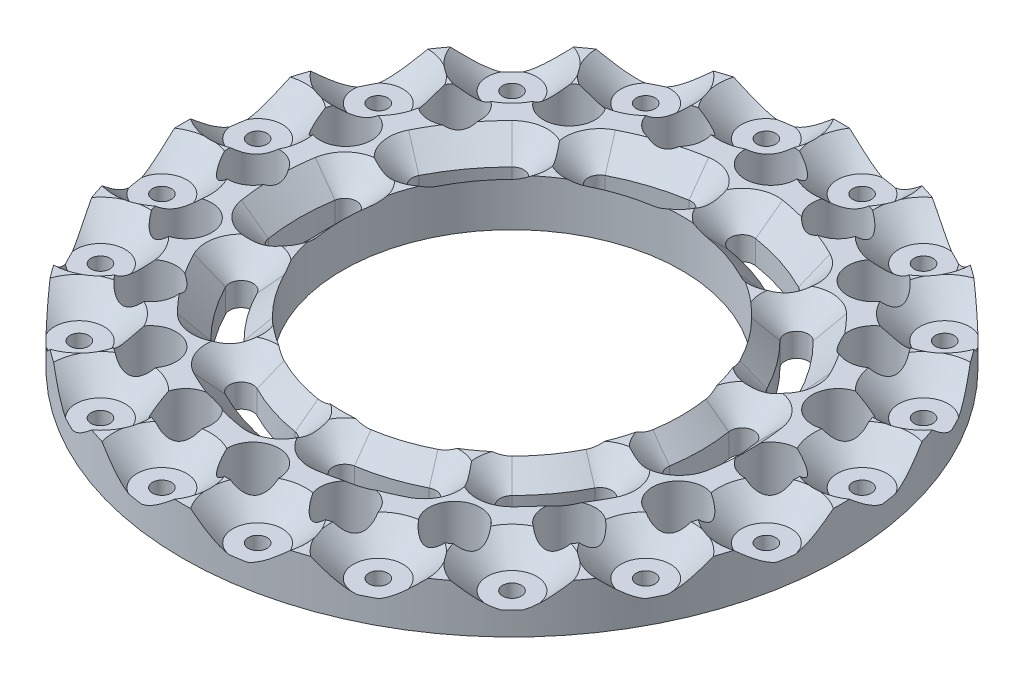
SolidWorks part; units mm, degrees
ref_plane "Front Plane" through (0, 0, 0) normal (0, 0, 1) x (1, 0, 0)
ref_plane "Top Plane" through (0, 0, 0) normal (0, 1, 0) x (1, 0, 0)
ref_plane "Right Plane" through (0, 0, 0) normal (1, 0, 0) x (0, 0, -1)
sketch "Sketch1" plane through (0, 0, 0) normal (0, 1, 0) x (1, 0, 0)
  circle A1 centre (55, 0) radius 5.5
  circle A2 centre (52.3081, -16.9959) radius 5.5
  circle A3 centre (44.4959, -32.3282) radius 5.5
  circle A4 centre (32.3282, -44.4959) radius 5.5
  circle A5 centre (16.9959, -52.3081) radius 5.5
  circle A6 centre (0, -55) radius 5.5
  circle A7 centre (-16.9959, -52.3081) radius 5.5
  circle A8 centre (-32.3282, -44.4959) radius 5.5
  circle A9 centre (-44.4959, -32.3282) radius 5.5
  circle A10 centre (-52.3081, -16.9959) radius 5.5
  circle A11 centre (-55, 0) radius 5.5
  circle A12 centre (-52.3081, 16.9959) radius 5.5
  circle A13 centre (-44.4959, 32.3282) radius 5.5
  circle A14 centre (-32.3282, 44.4959) radius 5.5
  circle A15 centre (-16.9959, 52.3081) radius 5.5
  circle A16 centre (0, 55) radius 5.5
  circle A17 centre (16.9959, 52.3081) radius 5.5
  circle A18 centre (32.3282, 44.4959) radius 5.5
  circle A19 centre (44.4959, 32.3282) radius 5.5
  circle A20 centre (52.3081, 16.9959) radius 5.5
  circle A21 centre (0, 0) radius 36
  circle A22 centre (0, 0) radius 70
  circle A24 centre (64.1997, 10.1682) radius 2
  circle A25 centre (64.1997, -10.1682) radius 2
  circle A26 centre (57.9154, -29.5094) radius 2
  circle A27 centre (45.9619, -45.9619) radius 2
  circle A28 centre (29.5094, -57.9154) radius 2
  circle A29 centre (10.1682, -64.1997) radius 2
  circle A30 centre (-10.1682, -64.1997) radius 2
  circle A31 centre (-29.5094, -57.9154) radius 2
  circle A32 centre (-45.9619, -45.9619) radius 2
  circle A33 centre (-57.9154, -29.5094) radius 2
  circle A34 centre (-64.1997, -10.1682) radius 2
  circle A35 centre (-64.1997, 10.1682) radius 2
  circle A36 centre (-57.9154, 29.5094) radius 2
  circle A37 centre (-45.9619, 45.9619) radius 2
  circle A38 centre (-29.5094, 57.9154) radius 2
  circle A39 centre (-10.1682, 64.1997) radius 2
  circle A40 centre (10.1682, 64.1997) radius 2
  circle A41 centre (29.5094, 57.9154) radius 2
  circle A42 centre (45.9619, 45.9619) radius 2
  circle A43 centre (57.9154, 29.5094) radius 2
  point P46 (0, 0)
  point P92 (0, 0)
  dimension "D1" = 20
  dimension "D3" = 20
extrude "Boss-Extrude1" add sketch "Sketch1" along normal blind 10
sketch "Sketch3" plane through (0, 10, 0) normal (0, 1, 0) x (1, 0, 0)
  circle A0 centre (-57.9154, -29.5094) radius 5.25
  circle A1 centre (-64.1997, -10.1682) radius 5.25
  circle A2 centre (-64.1997, 10.1682) radius 5.25
  circle A3 centre (-57.9154, 29.5094) radius 5.25
  circle A4 centre (-45.9619, 45.9619) radius 5.25
  circle A5 centre (-29.5094, 57.9154) radius 5.25
  circle A6 centre (-10.1682, 64.1997) radius 5.25
  circle A7 centre (10.1682, 64.1997) radius 5.25
  circle A8 centre (29.5094, 57.9154) radius 5.25
  circle A9 centre (45.9619, 45.9619) radius 5.25
  circle A10 centre (57.9154, 29.5094) radius 5.25
  circle A11 centre (64.1997, 10.1682) radius 5.25
  circle A12 centre (64.1997, -10.1682) radius 5.25
  circle A13 centre (57.9154, -29.5094) radius 5.25
  circle A14 centre (45.9619, -45.9619) radius 5.25
  circle A15 centre (29.5094, -57.9154) radius 5.25
  circle A16 centre (10.1682, -64.1997) radius 5.25
  circle A17 centre (-10.1682, -64.1997) radius 5.25
  circle A18 centre (-29.5094, -57.9154) radius 5.25
  circle A19 centre (-45.9619, -45.9619) radius 5.25
  point P44 (0, 0)
  dimension "D1" = 20
extrude "Cut-Extrude3" cut sketch "Sketch3" against normal blind 5
chamfer "Chamfer2" distance 5 angle 45 20 edges at (-53.2376, 10, 27.1259) (-42.2496, 10, 42.2496) (-27.1259, 10, 53.2376) (-9.347, 10, 59.0144) (9.347, 10, 59.0144) (27.1259, 10, 53.2376) (42.2496, 10, 42.2496) (53.2376, 10, 27.1259) (59.0144, 10, 9.347) (59.0144, 10, -9.347) (53.2376, 10, -27.1259) (42.2496, 10, -42.2496) (27.1259, 10, -53.2376) (9.347, 10, -59.0144) (-9.347, 10, -59.0144) (-27.1259, 10, -53.2376) (-42.2496, 10, -42.2496) (-53.2376, 10, -27.1259) (-59.0144, 10, -9.347) (-59.0144, 10, 9.347)
sketch "Sketch4" plane through (0, 10, 0) normal (0, 1, 0) x (1, 0, 0)
  line L0 (-49.5, 0) -> (-36, 0)
  line L1 (0, 0) -> (-49.5, 0)
  line L2 (0, 0) -> (-48.8906, 7.7435)
  line L3 (0, 0) -> (-48.8906, -7.7435)
  circle A0 centre (0, 0) radius 36
  circle A1 centre (0, 0) radius 49.5
  arc A3 (-42.2237, 6.6876) -> (-42.2237, -6.6876) centre (0, 0) ccw construction
  arc A4 (-44.6929, 7.0787) -> (-44.6929, -7.0787) centre (0, 0) ccw
  arc A5 (-39.7545, 6.2965) -> (-39.7545, -6.2965) centre (0, 0) ccw
  arc A6 (-39.7545, 6.2965) -> (-44.6929, 7.0787) centre (-42.2237, 6.6876) ccw
  arc A7 (-44.6929, -7.0787) -> (-39.7545, -6.2965) centre (-42.2237, -6.6876) ccw
  arc A8 (-30.2288, 30.2288) -> (-38.0905, 19.4081) centre (0, 0) ccw construction
  arc A9 (-31.9966, 31.9966) -> (-40.318, 20.5431) centre (0, 0) ccw
  arc A10 (-28.461, 28.461) -> (-35.863, 18.2731) centre (0, 0) ccw
  arc A11 (-28.461, 28.461) -> (-31.9966, 31.9966) centre (-30.2288, 30.2288) ccw
  arc A12 (-40.318, 20.5431) -> (-35.863, 18.2731) centre (-38.0905, 19.4081) ccw
  arc A13 (-6.6876, 42.2237) -> (-19.4081, 38.0905) centre (0, 0) ccw construction
  arc A14 (-7.0787, 44.6929) -> (-20.5431, 40.318) centre (0, 0) ccw
  arc A15 (-6.2965, 39.7545) -> (-18.2731, 35.863) centre (0, 0) ccw
  arc A16 (-6.2965, 39.7545) -> (-7.0787, 44.6929) centre (-6.6876, 42.2237) ccw
  arc A17 (-20.5431, 40.318) -> (-18.2731, 35.863) centre (-19.4081, 38.0905) ccw
  arc A18 (19.4081, 38.0905) -> (6.6876, 42.2237) centre (0, 0) ccw construction
  arc A19 (20.5431, 40.318) -> (7.0787, 44.6929) centre (0, 0) ccw
  arc A20 (18.2731, 35.863) -> (6.2965, 39.7545) centre (0, 0) ccw
  arc A21 (18.2731, 35.863) -> (20.5431, 40.318) centre (19.4081, 38.0905) ccw
  arc A22 (7.0787, 44.6929) -> (6.2965, 39.7545) centre (6.6876, 42.2237) ccw
  arc A23 (38.0905, 19.4081) -> (30.2288, 30.2288) centre (0, 0) ccw construction
  arc A24 (40.318, 20.5431) -> (31.9966, 31.9966) centre (0, 0) ccw
  arc A25 (35.863, 18.2731) -> (28.461, 28.461) centre (0, 0) ccw
  arc A26 (35.863, 18.2731) -> (40.318, 20.5431) centre (38.0905, 19.4081) ccw
  arc A27 (31.9966, 31.9966) -> (28.461, 28.461) centre (30.2288, 30.2288) ccw
  arc A28 (42.2237, -6.6876) -> (42.2237, 6.6876) centre (0, 0) ccw construction
  arc A29 (44.6929, -7.0787) -> (44.6929, 7.0787) centre (0, 0) ccw
  arc A30 (39.7545, -6.2965) -> (39.7545, 6.2965) centre (0, 0) ccw
  arc A31 (39.7545, -6.2965) -> (44.6929, -7.0787) centre (42.2237, -6.6876) ccw
  arc A32 (44.6929, 7.0787) -> (39.7545, 6.2965) centre (42.2237, 6.6876) ccw
  arc A33 (30.2288, -30.2288) -> (38.0905, -19.4081) centre (0, 0) ccw construction
  arc A34 (31.9966, -31.9966) -> (40.318, -20.5431) centre (0, 0) ccw
  arc A35 (28.461, -28.461) -> (35.863, -18.2731) centre (0, 0) ccw
  arc A36 (28.461, -28.461) -> (31.9966, -31.9966) centre (30.2288, -30.2288) ccw
  arc A37 (40.318, -20.5431) -> (35.863, -18.2731) centre (38.0905, -19.4081) ccw
  arc A38 (6.6876, -42.2237) -> (19.4081, -38.0905) centre (0, 0) ccw construction
  arc A39 (7.0787, -44.6929) -> (20.5431, -40.318) centre (0, 0) ccw
  arc A40 (6.2965, -39.7545) -> (18.2731, -35.863) centre (0, 0) ccw
  arc A41 (6.2965, -39.7545) -> (7.0787, -44.6929) centre (6.6876, -42.2237) ccw
  arc A42 (20.5431, -40.318) -> (18.2731, -35.863) centre (19.4081, -38.0905) ccw
  arc A43 (-19.4081, -38.0905) -> (-6.6876, -42.2237) centre (0, 0) ccw construction
  arc A44 (-20.5431, -40.318) -> (-7.0787, -44.6929) centre (0, 0) ccw
  arc A45 (-18.2731, -35.863) -> (-6.2965, -39.7545) centre (0, 0) ccw
  arc A46 (-18.2731, -35.863) -> (-20.5431, -40.318) centre (-19.4081, -38.0905) ccw
  arc A47 (-7.0787, -44.6929) -> (-6.2965, -39.7545) centre (-6.6876, -42.2237) ccw
  arc A48 (-38.0905, -19.4081) -> (-30.2288, -30.2288) centre (0, 0) ccw construction
  arc A49 (-40.318, -20.5431) -> (-31.9966, -31.9966) centre (0, 0) ccw
  arc A50 (-35.863, -18.2731) -> (-28.461, -28.461) centre (0, 0) ccw
  arc A51 (-35.863, -18.2731) -> (-40.318, -20.5431) centre (-38.0905, -19.4081) ccw
  arc A52 (-31.9966, -31.9966) -> (-28.461, -28.461) centre (-30.2288, -30.2288) ccw
  point P6 (-42.75, 0)
  point P13 (-42.75, 0)
  point P22 (-34.5855, 25.1278)
  point P29 (-13.2105, 40.6577)
  point P36 (13.2105, 40.6577)
  point P43 (34.5855, 25.1278)
  point P50 (42.75, 0)
  point P57 (34.5855, -25.1278)
  point P64 (13.2105, -40.6577)
  point P71 (-13.2105, -40.6577)
  point P78 (-34.5855, -25.1278)
  point P83 (0, 0)
  dimension "D2" = 10
  dimension "D1" = 9
extrude "Cut-Extrude4" cut sketch "Sketch4" against normal through all contours A29 A32 A30 A31 | A34 A37 A35 A36 | A39 A42 A40 A41 | A44 A47 A45 A46 | A49 A52 A50 A51 | A9 A12 A10 A11 | A14 A17 A15 A16 | A19 A22 A20 A21 | A24 A27 A25 A26 | A5 A7 A4 A6 region at (-34.3792, 10, -24.978) region at (-13.1317, 10, -40.4152) region at (13.1317, 10, -40.4152) region at (34.3792, 10, -24.978) region at (42.4951, 10, 0) region at (34.3792, 10, 24.978) region at (13.1317, 10, 40.4152) region at (-13.1317, 10, 40.4152) region at (-34.3792, 10, 24.978)
chamfer "Chamfer3" distance 5 angle 45 40 edges at (-45.25, 10, 0) (-41.8326, 10, -9.1568) (-41.8326, 10, 9.1568) (-40.25, 10, 0) (-36.608, 10, 26.5973) (-39.2255, 10, 17.1806) (-28.461, 10, 31.9966) (-32.5629, 10, 23.6584) (-13.983, 10, 43.0353) (-21.6356, 10, 36.9556) (-4.2184, 10, 42.6148) (-12.4379, 10, 38.28) (13.983, 10, 43.0353) (4.2184, 10, 42.6148) (21.6356, 10, 36.9556) (12.4379, 10, 38.28) (36.608, 10, 26.5973) (28.461, 10, 31.9966) (39.2255, 10, 17.1806) (32.5629, 10, 23.6584) (40.25, 10, 0) (41.8326, 10, 9.1568) (41.8326, 10, -9.1568) (45.25, 10, 0) (32.5629, 10, -23.6584) (39.2255, 10, -17.1806) (28.461, 10, -31.9966) (36.608, 10, -26.5973) (12.4379, 10, -38.28) (21.6356, 10, -36.9556) (4.2184, 10, -42.6148) (13.983, 10, -43.0353) (-12.4379, 10, -38.28) (-4.2184, 10, -42.6148) (-21.6356, 10, -36.9556) (-13.983, 10, -43.0353) (-32.5629, 10, -23.6584) (-28.461, 10, -31.9966) (-39.2255, 10, -17.1806) (-36.608, 10, -26.5973)
